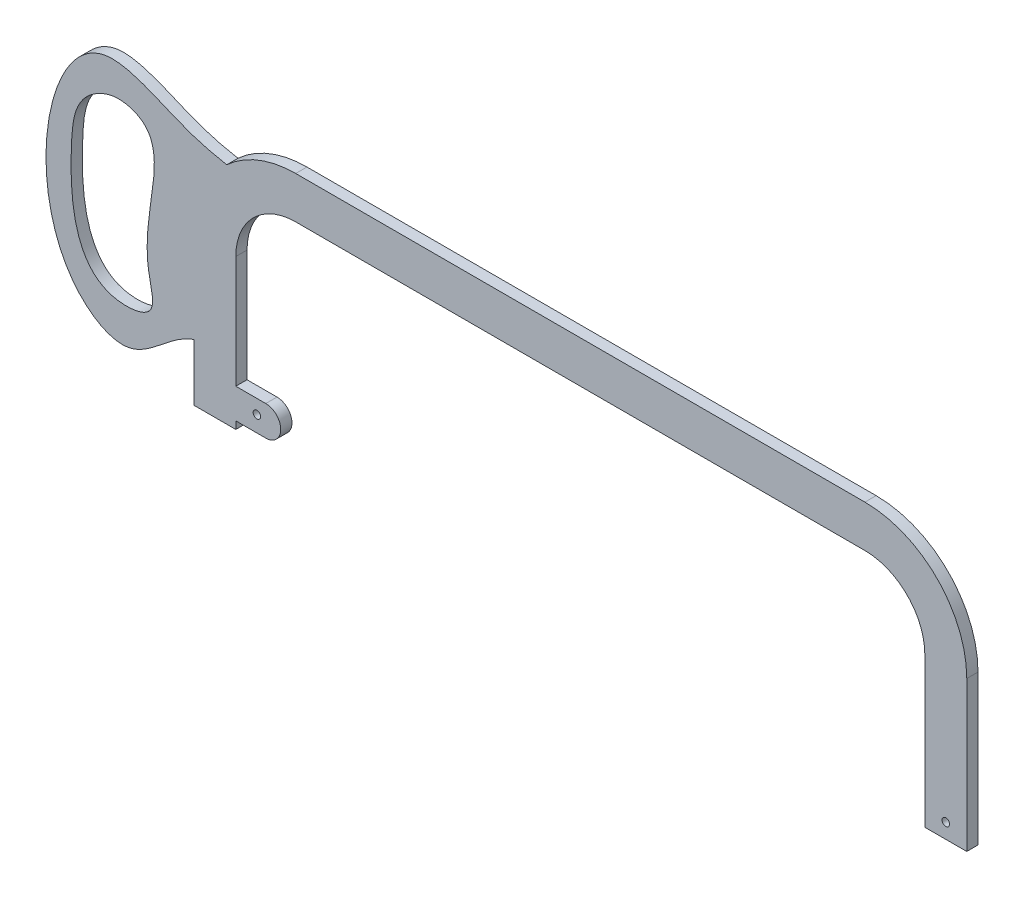
SolidWorks part; units mm, degrees
ref_plane "Front Plane" through (0, 0, 0) normal (0, 0, 1) x (1, 0, 0)
ref_plane "Top Plane" through (0, 0, 0) normal (0, 1, 0) x (1, 0, 0)
ref_plane "Right Plane" through (0, 0, 0) normal (1, 0, 0) x (0, 0, -1)
sketch "Sketch2" plane through (0, 0, 0) normal (0, 0, 1) x (1, 0, 0)
  line L0 (-176.2528, 0) -> (-176.2528, 63.5)
  line L1 (-150.8528, 88.9) -> (90.4472, 88.9)
  line L2 (115.8472, 63.5) -> (115.8472, 0)
  line L3 (115.8472, 0) -> (133.6272, 0)
  line L4 (133.6272, 0) -> (133.6272, 63.5)
  line L5 (90.4472, 106.68) -> (-150.8528, 106.68)
  line L6 (-194.0328, 63.5) -> (-194.0328, 0)
  line L7 (-194.0328, 0) -> (-176.2528, 0)
  arc A0 (-176.2528, 63.5) -> (-150.8528, 88.9) centre (-150.8528, 63.5) cw
  arc A1 (115.8472, 63.5) -> (90.4472, 88.9) centre (90.4472, 63.5) ccw
  arc A2 (-194.0328, 63.5) -> (-150.8528, 106.68) centre (-150.8528, 63.5) cw
  arc A3 (133.6272, 63.5) -> (90.4472, 106.68) centre (90.4472, 63.5) ccw
  dimension "D4" = 63.5
  dimension "D1" = 17.78
  dimension "D2" = 17.78
  dimension "D3" = 241.3
extrude "Extrude1" add sketch "Sketch2" along normal mid plane 4.7625
sketch "Sketch4" plane through (0, 0, 2.3813) normal (0, 0, 1) x (1, 0, 0)
  line L0 (-176.2528, 3.175) -> (-163.5528, 3.175)
  line L1 (-176.2528, 0) -> (-176.2528, 63.5) construction
  line L2 (-176.2528, 15.875) -> (-163.5528, 15.875)
  line L3 (-194.0328, 0) -> (-176.2528, 0) construction
  line L4 (-176.2528, 15.875) -> (-176.2528, 3.175)
  arc A0 (-163.5528, 3.175) -> (-163.5528, 15.875) centre (-163.5528, 9.525) ccw
  dimension "D1" = 12.7
  dimension "D2" = 3.175
  dimension "D3" = 12.7
extrude "Extrude2" add sketch "Sketch4" against normal up to surface (4.7625 mm away) up to face at (-30.2028, 56.1306, -2.3813)
sketch "Sketch5" plane through (0, 0, 2.3813) normal (0, 0, 1) x (1, 0, 0)
  line L0 (133.6272, 0) -> (133.6272, 63.5) construction
  circle A0 centre (-167.3363, 9.9386) radius 1.5875
  circle A1 centre (124.7372, 6.35) radius 1.5875
  arc A2 (115.8472, 63.5) -> (90.4472, 88.9) centre (90.4472, 63.5) ccw construction
  point P4 (90.4472, 63.5)
  dimension "D1" = 3.175
  dimension "D2" = 57.15
  dimension "D3" = 8.89
extrude "Cut-Extrude1" cut sketch "Sketch5" against normal through all
sketch "Sketch6" plane through (0, 0, 2.3813) normal (0, 0, 1) x (1, 0, 0)
  line L1 (-163.5001, 92.9767) -> (-185.371, 71.1058)
  line L2 (-185.371, 71.1058) -> (-185.371, 24.5413)
  spline S0 degree 3 poles (-163.5001, 92.9767) (-174.2158, 94.2301) (-196.7764, 96.8689) (-252.8592, 130.1247) (-269.4265, 29.7933) (-217.0907, -1.2909) (-200.7578, 26.3378) (-186.8997, 24.7198) (-185.371, 24.5413) knots 0 0 0 0 0.145422 0.306167 0.711218 0.81884 0.980016 1 1 1 1
  spline S1 degree 3 poles (-229.0238, 98.1269) (-244.4394, 89.2831) (-247.2836, 60.1055) (-244.9157, 18.8537) (-208.0817, 23.1237) (-220.298, 55.3932) (-201.0956, 90.7405) (-229.0238, 98.1269) (-244.4394, 89.2831) (-247.2836, 60.1055) knots -0.440904 -0.140512 -0.093904 0 0.110818 0.392382 0.473965 0.559096 0.859488 0.906096 1 1.110818 1.392382 1.473965 only from (-241.012, 88.8095) to (-241.012, 88.8095)
  point P2 (-249.3752, 94.5849)
extrude "Extrude3" add sketch "Sketch6" against normal up to surface (4.7625 mm away) up to face at (126.3247, 6.35, -2.3813)
